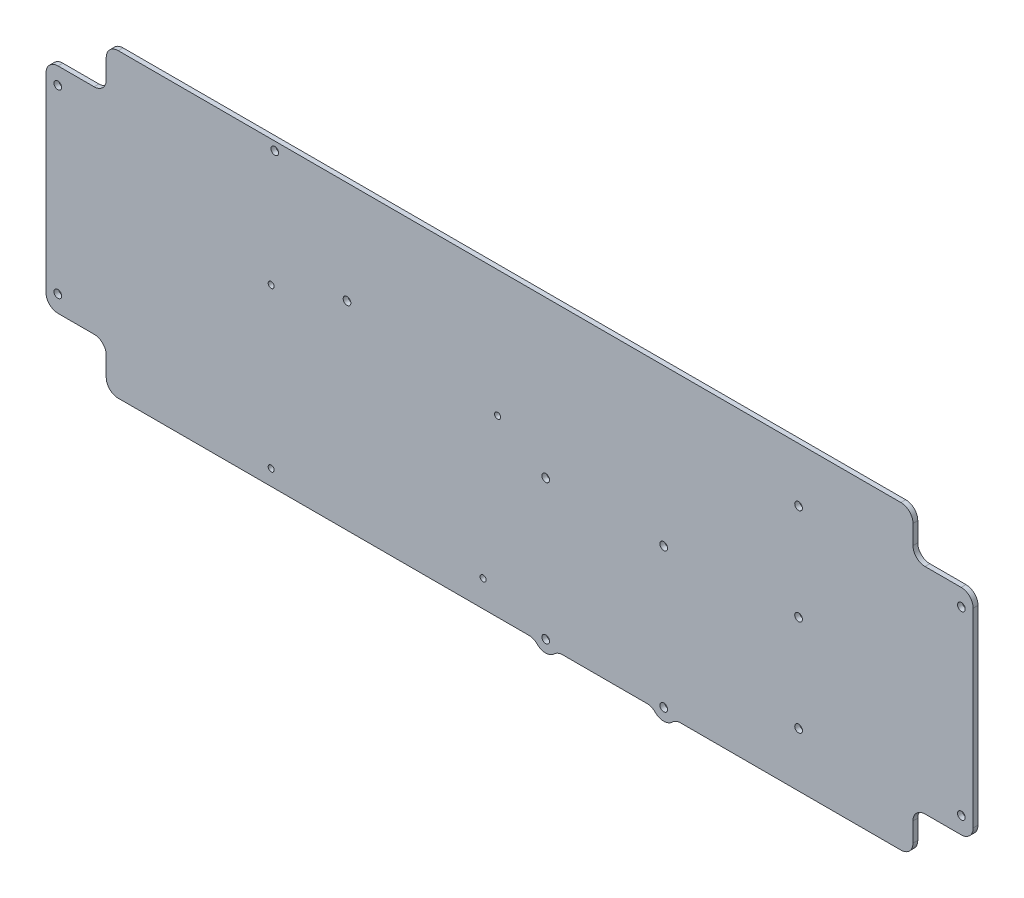
SolidWorks part; units mm, degrees
material "2014 Alloy"
ref_plane "Plan de face" through (0, 0, 0) normal (0, 0, 1) x (1, 0, 0)
ref_plane "Plan de dessus" through (0, 0, 0) normal (0, 1, 0) x (1, 0, 0)
ref_plane "Plan de droite" through (0, 0, 0) normal (1, 0, 0) x (0, 0, -1)
sketch "Sketch1" plane through (0, 0, 0) normal (0, 0, 1) x (1, 0, 0)
  line L1 (-192.5, 62.5) -> (192.5, 62.5)
  line L2 (-192.5, 62.5) -> (-192.5, -62.5)
  line L3 (-192.5, -62.5) -> (192.5, -62.5)
  line L4 (192.5, 62.5) -> (192.5, -62.5)
  line L5 (-192.5, 62.5) -> (192.5, -62.5) construction
  line L6 (-192.5, -62.5) -> (192.5, 62.5) construction
  point P0 (0, 0)
  dimension "D1" = 125
  dimension "D2" = 385
extrude "Boss-Extrude1" add sketch "Sketch1" along normal blind 2
sketch "Sketch2" plane through (0, 0, 2) normal (0, 0, 1) x (1, 0, 0)
  line L1 (-187.6, 37.5) -> (187.6, 37.5) construction
  line L2 (-187.6, 37.5) -> (-187.6, -37.5) construction
  line L3 (-187.6, -37.5) -> (187.6, -37.5) construction
  line L4 (187.6, 37.5) -> (187.6, -37.5) construction
  line L5 (-187.6, 37.5) -> (187.6, -37.5) construction
  line L6 (-187.6, -37.5) -> (187.6, 37.5) construction
  circle A0 centre (-187.6, 37.5) radius 1.6
  circle A1 centre (-187.6, -37.5) radius 1.6
  circle A2 centre (187.6, 37.5) radius 1.6
  circle A3 centre (187.6, -37.5) radius 1.6
  point P0 (0, 0)
  dimension "D1" = 75
  dimension "D2" = 375.2
extrude "Fixing_holes" cut sketch "Sketch2" against normal through all
sketch "Sketch3" plane through (0, 0, 2) normal (0, 0, 1) x (1, 0, 0)
  line L1 (-192.5, 62.5) -> (-167.5, 62.5)
  line L2 (-192.5, 62.5) -> (-192.5, 44.5)
  line L3 (-192.5, 44.5) -> (-167.5, 44.5)
  line L4 (-167.5, 62.5) -> (-167.5, 44.5)
  dimension "D1" = 18
  dimension "D2" = 25
extrude "Cut-Extrude2" cut sketch "Sketch3" against normal through all
mirror "Mirror1" about plane through (0, 0, 0) normal (0, 1, 0) of "Cut-Extrude2"
mirror "Mirror2" about plane through (0, 0, 0) normal (1, 0, 0) of "Mirror1"
sketch "Sketch4" plane through (0, 0, 2) normal (0, 0, 1) x (1, 0, 0)
  line L0 (-99, 10) -> (-5, 10) construction
  line L1 (-99, 10) -> (-99, -56) construction
  circle A0 centre (-99, 10) radius 1.25
  circle A1 centre (-99, -56) radius 1.25
  circle A2 centre (-5, 10) radius 1.25
  circle A3 centre (-11, -51.5) radius 1.25
  dimension "D4" = 66
  dimension "D5" = 94
  dimension "D7" = 61.5
  dimension "D8" = 6
  dimension "D1" = 5
  dimension "D2" = 10
extrude "Cave_board_holes" cut sketch "Sketch4" against normal through all
sketch "Sketch5" plane through (0, 0, 2) normal (0, 0, 1) x (1, 0, 0)
  line L1 (15, -2.4) -> (64, -2.4) construction
  line L2 (15, -2.4) -> (15, -60.4) construction
  line L3 (15, -60.4) -> (64, -60.4) construction
  line L4 (64, -2.4) -> (64, -60.4) construction
  circle A0 centre (15, -2.4) radius 1.6
  circle A1 centre (15, -60.4) radius 1.6
  circle A2 centre (64, -2.4) radius 1.6
  circle A3 centre (64, -60.4) radius 1.6
  dimension "D1" = 58
  dimension "D2" = 49
  dimension "D3" = 15
  dimension "D4" = 2.4
extrude "RPi_holes" cut sketch "Sketch5" against normal through all
sketch "Sketch6" plane through (0, 0, 2) normal (0, 0, 1) x (1, 0, 0)
  line L1 (-97.5, 59) -> (-67.5, 59) construction
  line L2 (-97.5, 59) -> (-97.5, 20) construction
  line L3 (-97.5, 20) -> (-67.5, 20) construction
  line L4 (-67.5, 59) -> (-67.5, 20) construction
  circle A0 centre (-97.5, 59) radius 1.6
  circle A3 centre (-67.5, 20) radius 1.6
  dimension "D1" = 39
  dimension "D2" = 30
  dimension "D3" = 67.5
  dimension "D4" = 20
extrude "buzzer_holes" cut sketch "Sketch6" against normal through all
sketch "Sketch7" plane through (0, 0, 2) normal (0, 0, 1) x (1, 0, 0)
  line L0 (0, 0) -> (178.5314, 0) construction
  circle A0 centre (120, 0) radius 1.6
  circle A1 centre (120, 40) radius 1.6
  circle A2 centre (120, -40) radius 1.6
  dimension "D4" = 120
  dimension "D5" = 40
extrude "relays_holes" cut sketch "Sketch7" against normal through all
sketch "Sketch8" plane through (0, 0, 2) normal (0, 0, 1) x (1, 0, 0)
  line L0 (-167.5, -62.5) -> (167.5, -62.5) construction
  line L2 (10.4624, -62.5) -> (19.5376, -62.5)
  line L3 (59.4624, -62.5) -> (68.5376, -62.5)
  arc A0 (10.4624, -62.5) -> (19.5376, -62.5) centre (15, -60.4) ccw
  arc A1 (59.4624, -62.5) -> (68.5376, -62.5) centre (64, -60.4) ccw
  dimension "D1" = 10
  dimension "D2" = 10
extrude "Boss-Extrude2" add sketch "Sketch8" against normal up to surface (2 mm away) up to face at (121.6, -40, 0)
fillet "Fillet1" radius 5 16 edges at (68.5376, -62.5, 1) (59.4624, -62.5, 1) (19.5376, -62.5, 1) (10.4624, -62.5, 1) (-192.5, 44.5, 1) (-167.5, 44.5, 1) (-167.5, 62.5, 1) (-167.5, -62.5, 1) (-167.5, -44.5, 1) (-192.5, -44.5, 1) (167.5, -62.5, 1) (167.5, -44.5, 1) (192.5, -44.5, 1) (192.5, 44.5, 1) (167.5, 44.5, 1) (167.5, 62.5, 1)
sketch "Sketch9" plane through (0, 0, 2) normal (0, 0, 1) x (1, 0, 0)
  line L0 (-192.5, 39.5) -> (-192.5, -39.5) construction
  line L1 (-162.5, -62.5) -> (7.958, -62.5) construction
  point P0 (-192.5, -62.5)
